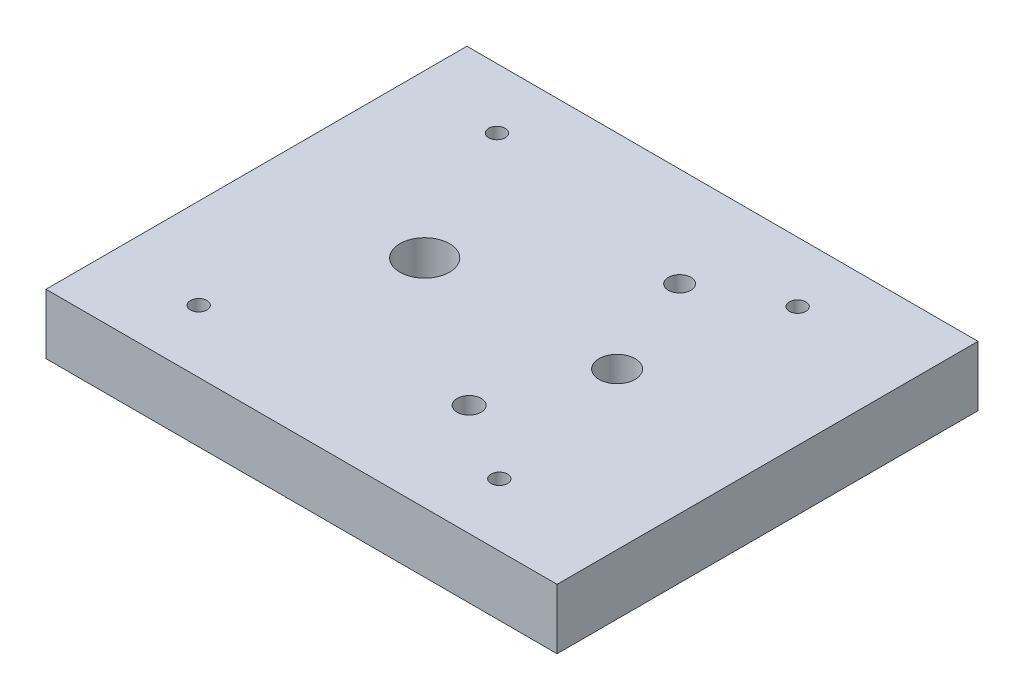
SolidWorks part; units mm, degrees
ref_plane "Front Plane" through (0, 0, 0) normal (0, 0, 1) x (1, 0, 0)
ref_plane "Top Plane" through (0, 0, 0) normal (0, 1, 0) x (1, 0, 0)
ref_plane "Right Plane" through (0, 0, 0) normal (1, 0, 0) x (0, 0, -1)
sketch "Sketch1" plane through (0, 0, 0) normal (0, 1, 0) x (1, 0, 0)
  line L0 (0, 8.2993) -> (0, -7.906) construction
  line L1 (-42.5, 35) -> (42.5, 35)
  line L2 (-42.5, 35) -> (-42.5, -35)
  line L3 (-42.5, -35) -> (42.5, -35)
  line L4 (42.5, 35) -> (42.5, -35)
  line L5 (-42.5, 35) -> (42.5, -35) construction
  line L6 (-42.5, -35) -> (42.5, 35) construction
  line L7 (-12.4915, 0.1967) -> (14.4413, 0.1967) construction
  line L8 (9.5, 1) -> (10.7497, 1) construction
  line L9 (37.5085, 0.1967) -> (64.4413, 0.1967) construction
  line L11 (15.0001, 2.9838) -> (15.0001, -1.0162)
  line L13 (17.9999, 3.0162) -> (17.9999, -0.9838)
  line L14 (15.0001, 2.9838) -> (17.9999, -0.9838) construction
  line L15 (15.0001, -1.0162) -> (17.9999, 3.0162) construction
  circle A0 centre (-27.5, 25) radius 1.375
  circle A1 centre (22.5, 25) radius 1.375
  circle A2 centre (22.5, -24.6067) radius 1.375
  circle A3 centre (-27.5, -24.6067) radius 1.375
  circle A4 centre (16.5, 1) radius 10
  circle A5 centre (-15.52, 1) radius 20
  arc A6 (15.0001, 2.9838) -> (17.9999, 3.0162) centre (16.5217, 1.0001) cw
  arc A7 (15.0001, -1.0162) -> (17.9999, -0.9838) centre (16.4783, 0.9999) ccw
  circle A8 centre (16.4783, 0.9999) radius 4.5
  circle A12 centre (-15.52, 1) radius 4.125
  circle A13 centre (16.4783, 0.9999) radius 3
  circle A14 centre (9.5, 1) radius 14
  circle A17 centre (85.0307, -10.8481) radius 14
  circle A18 centre (86.1334, -28.3481) radius 2
  circle A19 centre (86.1334, 6.6519) radius 2
  circle A20 centre (9.5, 1) radius 14
  circle A21 centre (9.4072, 18.471) radius 1.875
  circle A22 centre (9.4014, -16.529) radius 2
  point P0 (0, 0)
  dimension "D3" = 15
  dimension "D6" = 2.75
  dimension "D7" = 26
  dimension "D10" = 32.02
  dimension "D11" = 9
  dimension "D12" = 7
  dimension "D13" = 3.75
  dimension "D15" = 1.1027
  dimension "D17" = 1.1027
  dimension "D20" = 8.25
  dimension "D21" = 6
  dimension "D1" = 85
  dimension "D2" = 70
  dimension "D4" = 10
  dimension "D8" = 4
  dimension "D9" = 3
  dimension "D18" = 36
  dimension "D19" = 4
  dimension "D22" = 28.9915
  dimension "D5" = 2
extrude "Boss-Extrude4" add sketch "Sketch1" along normal blind 10 contours L4 L1 L2 L3 A14 A4 A5 A2 A1 A0 A3 | A14 A5 | A14 A4 | A5 A14 A4 | A5 A14 | A4 A14 A8 | A8 A13 | A4 A14 A5 region at (0, 0, -33.8989) region at (23.9705, 0, -1) region at (22.3127, 0, -5.9551) region at (6.1628, 0, -1) region at (-5.0421, 0, -1) region at (0.1582, 0, -1) region at (12.1056, 0, -0.9999)
sketch "Sketch2" plane through (0, 10, 0) normal (0, 1, 0) x (1, 0, 0)
  circle A3 centre (-15.52, 1) radius 9.125
  circle A4 centre (-15.52, 1) radius 9.125
  dimension "D1" = 5
extrude "Cut-Extrude2" cut sketch "Sketch1<7>" along normal blind 2 contours A8
sketch "Sketch1<7>" plane through (0, 0, 0) normal (0, 1, 0) x (1, 0, 0) same geometry as "Sketch1"
